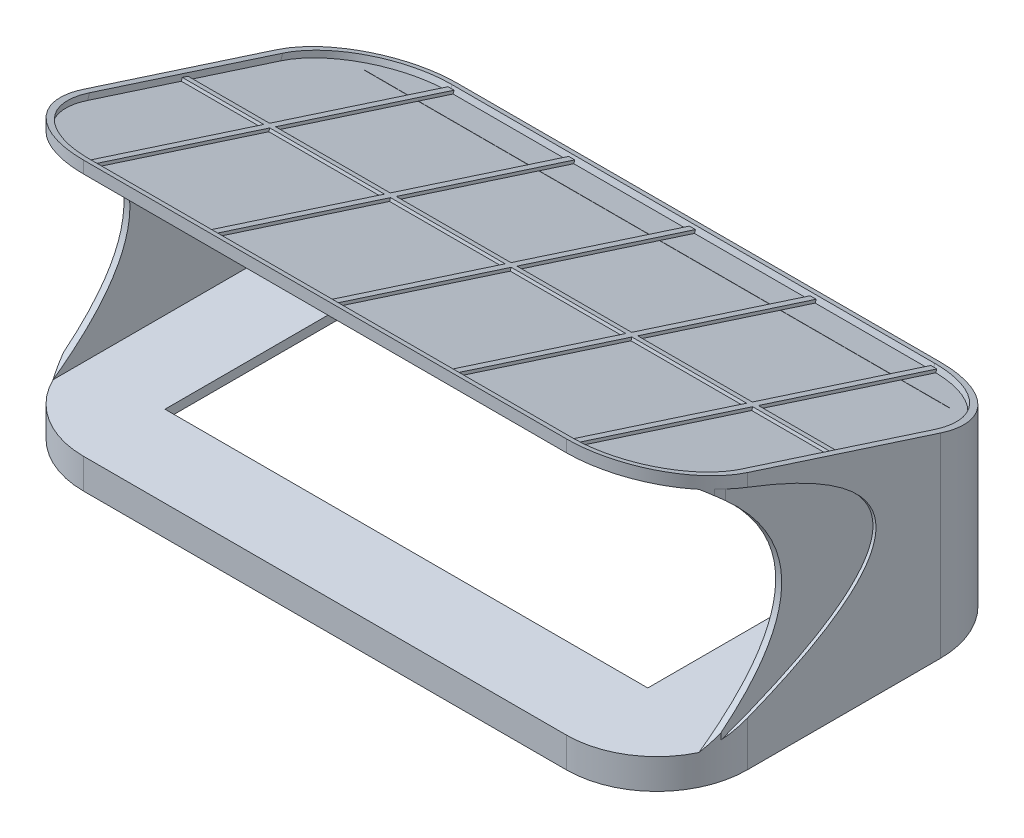
SolidWorks part; units mm, degrees
ref_plane "Front Plane" through (0, 0, 0) normal (0, 0, 1) x (1, 0, 0)
ref_plane "Top Plane" through (0, 0, 0) normal (0, 1, 0) x (1, 0, 0)
ref_plane "Right Plane" through (0, 0, 0) normal (1, 0, 0) x (0, 0, -1)
sketch "Sketch1" plane through (0, 0, 0) normal (0, 1, 0) x (1, 0, 0)
  line L1 (-80, 62) -> (80, 62)
  line L2 (-110, 32) -> (-110, -32)
  line L3 (-80, -62) -> (80, -62)
  line L4 (110, 32) -> (110, -32)
  line L5 (-110, 62) -> (110, -62) construction
  line L6 (-110, -62) -> (110, 62) construction
  arc A0 (-80, -62) -> (-110, -32) centre (-80, -32) cw
  arc A1 (-80, 62) -> (-110, 32) centre (-80, 32) ccw
  arc A2 (80, 62) -> (110, 32) centre (80, 32) cw
  arc A3 (80, -62) -> (110, -32) centre (80, -32) ccw
  point P0 (0, 0)
  dimension "D3" = 30
  dimension "D4" = 30
  dimension "D1" = 220
  dimension "D2" = 124
extrude "Boss-Extrude1" add sketch "Sketch1" along normal blind 95
sketch "Sketch2" plane through (0, 0, 62) normal (0, 0, 1) x (1, 0, 0)
  line L1 (80, 95) -> (80, 0) construction
  line L2 (80, 10) -> (-107, 10)
  line L4 (-80, 60) -> (-80, 95)
  line L6 (80, 10) -> (107, 10)
  line L8 (107, 60) -> (107, 10)
  line L9 (-80, 95) -> (80, 95) construction
  line L10 (80, 60) -> (-107, 60)
  line L12 (80, 60) -> (107, 60)
  line L14 (-107, 60) -> (-107, 10)
  line M2 (80, 0) -> (80, 95)
  line M4 (-80, 95) -> (-80, 0)
  dimension "D2" = 35
extrude "Cut-Extrude1" cut sketch "Sketch2" against normal blind 100 contours L10 L2 M2 M4 | L12 L6 L8 M2 | L10 L14 L2 M4 region at (93.5, 35, 62) region at (0, 35, 62) region at (-93.5, 35, 62)
sketch "Sketch3" plane through (0, 0, 0) normal (0, -1, 0) x (1, 0, 0)
  line L8 (-108, 32) -> (-108, -32)
  line L9 (-80, -60) -> (80, -60)
  line L10 (108, -32) -> (108, 32)
  line L11 (80, 60) -> (-80, 60)
  line L12 (-108, 32) -> (-108, -32)
  line L13 (-80, -60) -> (80, -60)
  line L14 (108, -32) -> (108, 32)
  line L15 (80, 60) -> (-80, 60)
  arc A8 (-80, 60) -> (-108, 32) centre (-80, 32) ccw
  arc A9 (-108, -32) -> (-80, -60) centre (-80, -32) ccw
  arc A10 (80, -60) -> (108, -32) centre (80, -32) ccw
  arc A11 (108, 32) -> (80, 60) centre (80, 32) ccw
  arc A12 (-80, 60) -> (-108, 32) centre (-80, 32) ccw
  arc A13 (-108, -32) -> (-80, -60) centre (-80, -32) ccw
  arc A14 (80, -60) -> (108, -32) centre (80, -32) ccw
  arc A15 (108, 32) -> (80, 60) centre (80, 32) ccw
  dimension "D1" = 2
extrude "Cut-Extrude2" cut sketch "Sketch3" against normal blind 7
sketch "Sketch4" plane through (110, 0, 0) normal (1, 0, 0) x (0, 0, -1)
  line L1 (62, 95) -> (62, 0) construction
  line L3 (62, 55) -> (-62, 95)
  line L4 (-62, 95) -> (62, 95)
  line L5 (62, 95) -> (62, 55)
  dimension "D1" = 40
extrude "Cut-Extrude3" cut sketch "Sketch4" against normal blind 232
sketch "Sketch5" plane through (110, 0, 0) normal (1, 0, 0) x (0, 0, -1)
  line L0 (-62, 95) -> (-62, 91)
  line L1 (-62, 95) -> (-62, 60) construction
  line L4 (-62, 91) -> (-62, 10)
  line L5 (-62, 10) -> (-45.0767, 10)
  spline S0 degree 2 poles (-62, 91) (2.9581, 51.5917) (-45.0767, 10) knots 0 0 0 1 1 1
  line M3 (-32, 85.3226) -> (-32, 0)
  dimension "D1" = 4
extrude "Cut-Extrude4" cut sketch "Sketch5" against normal blind 232 contours S0 L4 L5 M3 | S0 M3 region at (110, 46.6379, 48.3725) region at (110, 44.8826, 29.0626)
sketch "Sketch9" plane through (0, 67.9312, -21.9133) normal (0, 0.9517, -0.307) x (1, 0, 0)
  line L8 (108, -56.6489) -> (108, 10.5985)
  line L9 (80, 40.1208) -> (-80, 40.1208)
  line L10 (-108, 10.5985) -> (-108, -56.6489)
  line L11 (-80, -86.1712) -> (80, -86.1712)
  line L12 (108, -56.6489) -> (108, 10.5985)
  line L13 (80, 40.1208) -> (-80, 40.1208)
  line L14 (-108, 10.5985) -> (-108, -56.6489)
  line L15 (-80, -86.1712) -> (80, -86.1712)
  spline S0 degree 3 poles (-6691.3363, -1603.5855) (-969.6006, -479.5981) (135.4294, -135.9448) (107.3205, 17.1302) (107.1096, 18.044) (106.7291, 19.404) (106.5915, 19.8555) (106.2945, 20.7548) (106.135, 21.2028) (105.2904, 23.4097) (104.4609, 25.0895) (102.9868, 27.4811) (102.4569, 28.2568) (101.6018, 29.3868) (101.3059, 29.7589) (100.6977, 30.4862) (100.386, 30.8409) (98.7895, 32.5707) (97.3925, 33.8153) (95.1137, 35.469) (94.3219, 35.9852) (92.6788, 36.9388) (91.84, 37.369) (89.2731, 38.5234) (87.4952, 39.1127) (85.1857, 39.6142) (84.7182, 39.7028) (83.7806, 39.8547) (83.3107, 39.9179) (-71.7655, 56.5893) (-346.2988, -1281.7973) (-996.5228, -6864.9188) knots -10.201253 -10.201253 -10.201253 -10.201253 0.125 0.125 0.1875 0.1875 0.21875 0.21875 0.25 0.25 0.375 0.375 0.4375 0.4375 0.46875 0.46875 0.5 0.5 0.625 0.625 0.6875 0.6875 0.75 0.75 0.875 0.875 0.90625 0.90625 0.9375 0.9375 11.194358 11.194358 11.194358 11.194358 only from (108, 10.5985) to (80, 40.1208)
  spline S1 degree 3 poles (1505.2125, -6768.082) (363.5386, -945.0612) (49.283, 68.5457) (-86.5136, 39.3276) (-87.4214, 39.082) (-88.7703, 38.6393) (-89.2184, 38.4791) (-90.1, 38.1374) (-90.5348, 37.9556) (-92.6791, 36.9933) (-94.3009, 36.0543) (-96.5954, 34.3959) (-97.3385, 33.7991) (-98.7472, 32.5475) (-99.4168, 31.89) (-100.6889, 30.5136) (-101.2913, 29.7948) (-102.1447, 28.6706) (-102.4208, 28.2882) (-102.956, 27.5079) (-103.2154, 27.1095) (-104.457, 25.0991) (-105.2858, 23.4175) (-106.2936, 20.7903) (-106.59, 19.8969) (-106.9742, 18.53) (-107.0921, 18.0699) (-107.3056, 17.149) (-107.4016, 16.6871) (-140.0462, -160.6082) (1368.8696, -538.0562) (6731.0448, -1416.9883) knots -9.077061 -9.077061 -9.077061 -9.077061 0.125 0.125 0.1875 0.1875 0.21875 0.21875 0.25 0.25 0.375 0.375 0.4375 0.4375 0.5 0.5 0.5625 0.5625 0.59375 0.59375 0.625 0.625 0.75 0.75 0.8125 0.8125 0.84375 0.84375 0.875 0.875 12.803904 12.803904 12.803904 12.803904 only from (-80, 40.1208) to (-108, 10.5985)
  spline S2 degree 3 poles (6691.3363, 1557.5351) (969.6006, 433.5476) (-135.4294, 89.8944) (-107.3205, -63.1806) (-107.1096, -64.0945) (-106.7291, -65.4544) (-106.5915, -65.9059) (-106.2945, -66.8052) (-106.135, -67.2532) (-105.2904, -69.4601) (-104.4609, -71.1399) (-102.9868, -73.5315) (-102.4569, -74.3073) (-101.6018, -75.4373) (-101.3059, -75.8093) (-100.6977, -76.5366) (-100.386, -76.8913) (-98.7895, -78.6211) (-97.3925, -79.8658) (-95.1137, -81.5194) (-94.3219, -82.0356) (-92.6788, -82.9892) (-91.84, -83.4194) (-89.2731, -84.5738) (-87.4952, -85.1631) (-85.1857, -85.6646) (-84.7182, -85.7533) (-83.7806, -85.9051) (-83.3107, -85.9683) (71.7655, -102.6397) (346.2988, 1235.7469) (996.5228, 6818.8684) knots -10.201253 -10.201253 -10.201253 -10.201253 0.125 0.125 0.1875 0.1875 0.21875 0.21875 0.25 0.25 0.375 0.375 0.4375 0.4375 0.46875 0.46875 0.5 0.5 0.625 0.625 0.6875 0.6875 0.75 0.75 0.875 0.875 0.90625 0.90625 0.9375 0.9375 11.194358 11.194358 11.194358 11.194358 only from (-108, -56.6489) to (-80, -86.1712)
  spline S3 degree 3 poles (-1505.2125, 6722.0316) (-363.5386, 899.0108) (-49.283, -114.5961) (86.5136, -85.378) (87.4214, -85.1325) (88.7703, -84.6898) (89.2184, -84.5295) (90.1, -84.1878) (90.5348, -84.006) (92.6791, -83.0438) (94.3009, -82.1047) (96.5954, -80.4464) (97.3385, -79.8496) (98.7472, -78.5979) (99.4168, -77.9404) (100.6889, -76.5641) (101.2913, -75.8452) (102.1447, -74.721) (102.4208, -74.3386) (102.956, -73.5583) (103.2154, -73.1599) (104.457, -71.1495) (105.2858, -69.468) (106.2936, -66.8407) (106.59, -65.9473) (106.9742, -64.5804) (107.0921, -64.1203) (107.3056, -63.1994) (107.4016, -62.7376) (140.0462, 114.5578) (-1368.8696, 492.0058) (-6731.0448, 1370.9379) knots -9.077061 -9.077061 -9.077061 -9.077061 0.125 0.125 0.1875 0.1875 0.21875 0.21875 0.25 0.25 0.375 0.375 0.4375 0.4375 0.5 0.5 0.5625 0.5625 0.59375 0.59375 0.625 0.625 0.75 0.75 0.8125 0.8125 0.84375 0.84375 0.875 0.875 12.803904 12.803904 12.803904 12.803904 only from (80, -86.1712) to (108, -56.6489)
  spline S4 degree 3 poles (108, 10.5985) (108, 12.4975) (107.8278, 14.3674) (107.3205, 17.1302) (107.1096, 18.044) (106.7291, 19.404) (106.5915, 19.8555) (106.2945, 20.7548) (106.135, 21.2028) (105.2904, 23.4097) (104.4609, 25.0895) (102.9868, 27.4811) (102.4569, 28.2568) (101.6018, 29.3868) (101.3059, 29.7589) (100.6977, 30.4862) (100.386, 30.8409) (98.7895, 32.5707) (97.3925, 33.8153) (95.1137, 35.469) (94.3219, 35.9852) (92.6788, 36.9388) (91.84, 37.369) (89.2731, 38.5234) (87.4952, 39.1127) (85.1857, 39.6142) (84.7182, 39.7028) (83.7806, 39.8547) (83.3107, 39.9179) (81.8976, 40.0698) (80.951, 40.1208) (80, 40.1208) knots 0 0 0 0 0.125 0.125 0.1875 0.1875 0.21875 0.21875 0.25 0.25 0.375 0.375 0.4375 0.4375 0.46875 0.46875 0.5 0.5 0.625 0.625 0.6875 0.6875 0.75 0.75 0.875 0.875 0.90625 0.90625 0.9375 0.9375 1 1 1 1
  spline S5 degree 3 poles (-80, 40.1208) (-81.9, 40.1208) (-83.7653, 39.919) (-86.5136, 39.3276) (-87.4214, 39.082) (-88.7703, 38.6393) (-89.2184, 38.4791) (-90.1, 38.1374) (-90.5348, 37.9556) (-92.6791, 36.9933) (-94.3009, 36.0543) (-96.5954, 34.3959) (-97.3385, 33.7991) (-98.7472, 32.5475) (-99.4168, 31.89) (-100.6889, 30.5136) (-101.2913, 29.7948) (-102.1447, 28.6706) (-102.4208, 28.2882) (-102.956, 27.5079) (-103.2154, 27.1095) (-104.457, 25.0991) (-105.2858, 23.4175) (-106.2936, 20.7903) (-106.59, 19.8969) (-106.9742, 18.53) (-107.0921, 18.0699) (-107.3056, 17.149) (-107.4016, 16.6871) (-107.8281, 14.3709) (-108, 12.4959) (-108, 10.5985) knots 0 0 0 0 0.125 0.125 0.1875 0.1875 0.21875 0.21875 0.25 0.25 0.375 0.375 0.4375 0.4375 0.5 0.5 0.5625 0.5625 0.59375 0.59375 0.625 0.625 0.75 0.75 0.8125 0.8125 0.84375 0.84375 0.875 0.875 1 1 1 1
  spline S6 degree 3 poles (-108, -56.6489) (-108, -58.5479) (-107.8278, -60.4178) (-107.3205, -63.1806) (-107.1096, -64.0945) (-106.7291, -65.4544) (-106.5915, -65.9059) (-106.2945, -66.8052) (-106.135, -67.2532) (-105.2904, -69.4601) (-104.4609, -71.1399) (-102.9868, -73.5315) (-102.4569, -74.3073) (-101.6018, -75.4373) (-101.3059, -75.8093) (-100.6977, -76.5366) (-100.386, -76.8913) (-98.7895, -78.6211) (-97.3925, -79.8658) (-95.1137, -81.5194) (-94.3219, -82.0356) (-92.6788, -82.9892) (-91.84, -83.4194) (-89.2731, -84.5738) (-87.4952, -85.1631) (-85.1857, -85.6646) (-84.7182, -85.7533) (-83.7806, -85.9051) (-83.3107, -85.9683) (-81.8976, -86.1202) (-80.951, -86.1712) (-80, -86.1712) knots 0 0 0 0 0.125 0.125 0.1875 0.1875 0.21875 0.21875 0.25 0.25 0.375 0.375 0.4375 0.4375 0.46875 0.46875 0.5 0.5 0.625 0.625 0.6875 0.6875 0.75 0.75 0.875 0.875 0.90625 0.90625 0.9375 0.9375 1 1 1 1
  spline S7 degree 3 poles (80, -86.1712) (81.9, -86.1712) (83.7653, -85.9694) (86.5136, -85.378) (87.4214, -85.1325) (88.7703, -84.6898) (89.2184, -84.5295) (90.1, -84.1878) (90.5348, -84.006) (92.6791, -83.0438) (94.3009, -82.1047) (96.5954, -80.4464) (97.3385, -79.8496) (98.7472, -78.5979) (99.4168, -77.9404) (100.6889, -76.5641) (101.2913, -75.8452) (102.1447, -74.721) (102.4208, -74.3386) (102.956, -73.5583) (103.2154, -73.1599) (104.457, -71.1495) (105.2858, -69.468) (106.2936, -66.8407) (106.59, -65.9473) (106.9742, -64.5804) (107.0921, -64.1203) (107.3056, -63.1994) (107.4016, -62.7376) (107.8281, -60.4213) (108, -58.5463) (108, -56.6489) knots 0 0 0 0 0.125 0.125 0.1875 0.1875 0.21875 0.21875 0.25 0.25 0.375 0.375 0.4375 0.4375 0.5 0.5 0.5625 0.5625 0.59375 0.59375 0.625 0.625 0.75 0.75 0.8125 0.8125 0.84375 0.84375 0.875 0.875 1 1 1 1
  dimension "D1" = 2
extrude "Cut-Extrude6" cut sketch "Sketch9" against normal blind 2
ref_plane "Plane2" through (-107, 0, 0) normal (1, 0, 0) x (0, 0, -1)
sketch "Sketch10" plane through (-107, 0, 0) normal (1, 0, 0) x (0, 0, -1)
  line L0 (62, 55) -> (62, 51)
  line L1 (62, 55) -> (62, 0) construction
  line L2 (-62, 10) -> (42, 10)
  line L3 (-62, 91) -> (62, 51)
  line L4 (42, 10) -> (42, 57.4516)
  line L5 (-62, 91) -> (-62, 10)
  dimension "D1" = 4
  dimension "D2" = 20
extrude "Cut-Extrude7" cut sketch "Sketch10" along normal blind 214 contours L3 L5 L2 L4 region at (-107, 42.8431, 14.527)
sketch "Sketch11" plane through (-110, 0, 0) normal (-1, 0, 0) x (0, 0, 1)
  line L0 (45.0767, 85.5409) -> (45.0767, 45.533)
  line L1 (45.0767, 45.533) -> (24.6619, 45.533)
  parabola Q0 (32, 65.5589) -> (32, 24.0929) focus (39.2849, 45.2504) apex (24.6619, 45.533) construction
  spline S0 degree 2 poles (45.0767, 85.5409) (23.6817, 65.2591) (24.6619, 45.533) knots 0 0 0 0.522908 0.522908 0.522908
extrude "Cut-Extrude8" cut sketch "Sketch11" against normal blind 231
sketch "Sketch14" plane through (110, 0, 0) normal (1, 0, 0) x (0, 0, -1)
  line L0 (-24.6619, 45.533) -> (-19.6619, 45.533)
  line L1 (-45.0767, 85.5409) -> (-45.0767, 10)
  spline S0 degree 2 poles (-45.0767, 85.5409) (5.8374, 46.3712) (-45.0767, 10) knots 0 0 0 1 1 1
  line M1 (-32, 85.3226) -> (-32, 70.133)
  spline M2 degree 2 poles (-45.0767, 85.5409) (-23.6817, 65.2591) (-24.6619, 45.533) knots 0 0 0 0.522908 0.522908 0.522908 only from (-32, 70.133) to (-24.6619, 45.533)
  spline M3 degree 2 poles (-62, 91) (2.9581, 51.5917) (-45.0767, 10) knots 0 0 0 1 1 1 only from (-24.6619, 45.533) to (-32, 24.0929)
  line M4 (-32, 24.0929) -> (-32, 0)
  dimension "D1" = 5
  dimension "D2" = 5
extrude "Cut-Extrude9" cut sketch "Sketch14" against normal blind 231 contours S0 L0 M3 M4 | S0 L0 M1 M2 | S0 L1 M4 M3 M2 M1 region at (110, 47.4906, 34.8939)
sketch "Sketch15" plane through (110, 0, 0) normal (1, 0, 0) x (0, 0, -1)
  line L0 (-19.6302, 46.3016) -> (10.3698, 45.7621)
  line L1 (-62, 91) -> (-45.0767, 10)
  parabola Q1 (-32, 73.751) -> (-32, 21.0711) focus (-33.619, 46.6861) apex (-19.6302, 46.3016) construction
  spline S0 degree 2 poles (-62, 91) (74.2043, 51.4054) (-45.0767, 10) knots 0 0 0 1 1 1
  spline M1 degree 2 poles (-45.0767, 85.5409) (5.8374, 46.3712) (-45.0767, 10) knots 0 0 0 1 1 1 only from (-32, 73.751) to (-32, 21.0711)
  line M2 (-32, 21.0711) -> (-32, 0)
  line M6 (-32, 85.3226) -> (-32, 73.751)
  dimension "D1" = 30
extrude "Cut-Extrude14" cut sketch "Sketch15" against normal blind 1 contours S0 L0 M1 M2 | S0 L1 M2 M1 M6 | S0 L0 M6 M1 region at (110, 50.6811, 27.9898)
fillet "Fillet1" radius 10 1 edges at (109, 82.5276, 39.6811)
sketch "Sketch16" plane through (-110, 0, 0) normal (-1, 0, 0) x (0, 0, 1)
  line L0 (19.6302, 46.3016) -> (-10.3698, 45.6132)
  line L1 (62, 91) -> (45.0767, 10)
  parabola Q0 (32, 73.751) -> (32, 21.0711) focus (33.619, 46.6861) apex (19.6302, 46.3016) construction
  spline S0 degree 2 poles (62, 91) (-74.2214, 51.1897) (45.0767, 10) knots 0 0 0 1 1 1
  spline M1 degree 2 poles (45.0767, 10) (-5.8374, 46.3712) (45.0767, 85.5409) knots 0 0 0 1 1 1 only from (32, 21.0711) to (32, 73.751)
  line M2 (32, 73.751) -> (32, 85.3226)
  line M6 (32, 0) -> (32, 21.0711)
  dimension "D1" = 30
extrude "Cut-Extrude15" cut sketch "Sketch16" against normal blind 1 contours L1 S0 M2 M1 M6 | S0 L0 M2 M1 | L0 S0 M6 M1 region at (-110, 50.6379, 27.9864)
fillet "Fillet2" radius 10 1 edges at (-109, 82.5105, 39.6811)
sketch "Sketch17" plane through (0, 0, -42) normal (0, 0, 1) x (1, 0, 0)
  line L0 (0, 58.7419) -> (0, 57.4516)
  line L1 (107, 58.7419) -> (-107, 58.7419) construction
  line L2 (107, 57.4516) -> (107, 10)
  line L3 (107, 10) -> (-107, 10) construction
  line L4 (107, 10) -> (107, 57.4516) construction
  line L5 (97, 57.4516) -> (97, 10)
  line L6 (107, 57.4516) -> (-107, 57.4516) construction
  line L7 (-97, 57.4516) -> (-97, 10)
  line L8 (-97, 57.4516) -> (97, 57.4516)
  line L9 (-97, 10) -> (97, 10)
  line L10 (0, 10) -> (0, 0)
  line M2 (-107, 10) -> (107, 10)
  line M4 (107, 57.4516) -> (-107, 57.4516)
  dimension "D1" = 10
extrude "Cut-Extrude16" cut sketch "Sketch17" against normal blind 6 contours L7 L9 L5 M4 M2 region at (0, 33.7258, -42)
fillet "Fillet3" radius 10 2 edges
ref_plane "Plane5" through (0, 66.9795, -21.6063) normal (0, 0.9517, -0.307) x (1, 0, 0)
sketch "Sketch34" plane through (0, 66.9795, -21.6063) normal (0, 0.9517, -0.307) x (1, 0, 0)
  line L0 (-39, -22.0252) -> (-39, 40.1208)
  line L2 (41, -22.0252) -> (41, 40.1208)
  line L4 (-1, -22.0252) -> (-39, -22.0252)
  line L6 (-41, -86.1712) -> (-39, -86.1712)
  line L7 (79, 40.1208) -> (79, -22.0252)
  line L8 (41, -86.1712) -> (41, -24.0252)
  line L9 (-81, 40.1208) -> (-81, -22.0252)
  line L10 (-39, -86.1712) -> (-39, -24.0252)
  line L11 (-1, 40.1208) -> (-1, -22.0252)
  line L12 (108, -22.0252) -> (81, -22.0252)
  line L13 (81, 40.1208) -> (81, -22.0252)
  line L14 (39, -86.1712) -> (39, -24.0252)
  line L15 (-79, 40.1208) -> (-79, -22.0252)
  line L16 (-41, -86.1712) -> (-41, -24.0252)
  line L17 (1, 40.1208) -> (1, -22.0252)
  line L18 (108, -24.0252) -> (81, -24.0252)
  line L19 (-81, 40.1208) -> (-39, 40.1208)
  line L20 (-81, -86.1712) -> (-79, -86.1712)
  line L21 (108, -22.0252) -> (108, -24.0252)
  line L22 (108, -22.0252) -> (108, -24.0252)
  line L23 (-108, -22.0252) -> (-108, -24.0252)
  line L24 (-1, -86.1712) -> (1, -86.1712)
  line L25 (-81, -22.0252) -> (-108, -22.0252)
  line L27 (79, -86.1712) -> (81, -86.1712)
  line L28 (-1, -24.0252) -> (-39, -24.0252)
  line L29 (39, -86.1712) -> (41, -86.1712)
  line L30 (-81, -24.0252) -> (-108, -24.0252)
  line L31 (1, -24.0252) -> (1, -86.1712)
  line L32 (-79, -24.0252) -> (-79, -86.1712)
  line L33 (79, 40.1208) -> (81, 40.1208)
  line L34 (-81, -24.0252) -> (-81, -86.1712)
  line L35 (39, 40.1208) -> (41, 40.1208)
  line L36 (-1, 40.1208) -> (1, 40.1208)
  line L37 (39, 40.1208) -> (41, 40.1208)
  line L38 (79, -24.0252) -> (79, -86.1712)
  line L40 (-1, -24.0252) -> (-1, -86.1712)
  line L41 (-41, -22.0252) -> (-41, 40.1208)
  line L42 (81, -24.0252) -> (81, -86.1712)
  line L43 (39, -24.0252) -> (1, -24.0252)
  line L44 (79, -24.0252) -> (41, -24.0252)
  line L45 (79, -22.0252) -> (41, -22.0252)
  line L46 (39, -22.0252) -> (39, 40.1208)
  line L48 (-41, -24.0252) -> (-79, -24.0252)
  line L49 (39, -22.0252) -> (1, -22.0252)
  line L50 (-41, -22.0252) -> (-79, -22.0252)
  arc A4 (-81, 40.1208) -> (-79, 40.1208) centre (-80, 40.1208) cw
  arc A5 (-81, -86.1712) -> (-79, -86.1712) centre (-80, -86.1712) ccw
  arc A6 (-39, -86.1712) -> (-41, -86.1712) centre (-40, -86.1712) cw
  arc A7 (-39, 40.1208) -> (-41, 40.1208) centre (-40, 40.1208) ccw
  arc A10 (108, -22.0252) -> (108, -24.0252) centre (108, -23.0252) cw
  point P4 (26.8677, -43.3557)
extrude "Boss-Extrude2" add sketch "Sketch34" against normal blind 1 contours L41 L50 L15 L19 L9 L25 L23 L30 L34 L20 L32 L48 L16 L6 L10 L28 L40 L24 L31 L43 L14 L29 L8 L44 L38 L27 L42 L18 L21 L12 L13 L33 L7 L45 L2 L35 L46 L49 L17 L36 L11 L4 L0 region at (0, 74.0483, 0.307)
sketch "Sketch35" plane through (0, 7, 0) normal (0, -1, 0) x (1, 0, 0)
  line L0 (80, 35) -> (-80, 35)
  line L5 (80, 35) -> (80, -35)
  line L6 (80, -35) -> (-80, -35)
  line L7 (-80, 35) -> (-80, -35)
  point P9 (0, 35)
extrude "Cut-Extrude17" cut sketch "Sketch35" against normal blind 10
